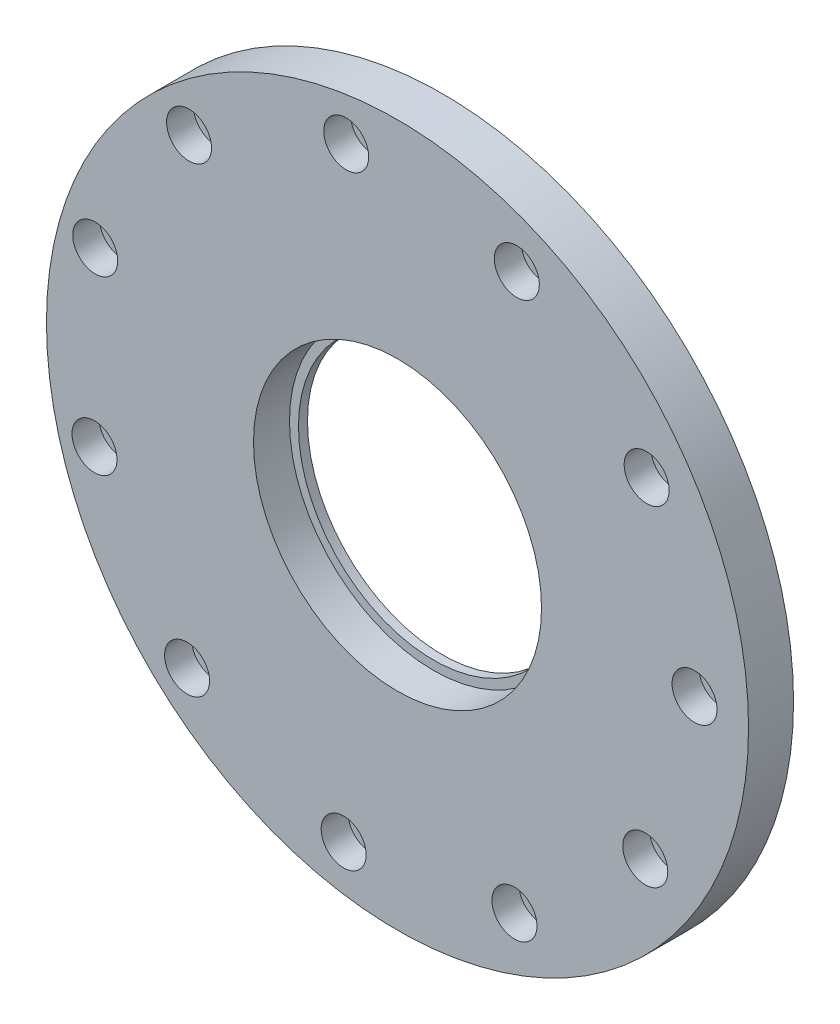
SolidWorks part; units mm, degrees
ref_plane "Front Plane" through (0, 0, 0) normal (0, 0, 1) x (1, 0, 0)
ref_plane "Top Plane" through (0, 0, 0) normal (0, 1, 0) x (1, 0, 0)
ref_plane "Right Plane" through (0, 0, 0) normal (1, 0, 0) x (0, 0, -1)
sketch "Sketch1" plane through (0, 0, 0) normal (0, 0, 1) x (1, 0, 0)
  circle A0 centre (0, 0) radius 39
  circle A1 centre (0, 0) radius 33 construction
  circle A2 centre (33, 0) radius 2.5
  circle A3 centre (27.5249, -18.359) radius 2.5
  circle A4 centre (12.9933, -30.8434) radius 2.5
  circle A5 centre (-5.981, -33.4897) radius 2.5
  circle A6 centre (-23.3739, -25.4576) radius 2.5
  circle A7 centre (-33.6633, -9.2972) radius 2.5
  circle A8 centre (-33.5823, 9.8606) radius 2.5
  circle A9 centre (-23.1566, 25.9334) radius 2.5
  circle A10 centre (-5.6964, 33.8182) radius 2.5
  circle A11 centre (13.2549, 31.0115) radius 2.5
  circle A12 centre (27.6804, 18.4046) radius 2.5
  circle A13 centre (0, 0) radius 16
  point P7 (-1, 0)
  point P28 (-1, 0.1438)
extrude "Boss-Extrude1" add sketch "Sketch1" along normal blind 3
sketch "Sketch2" plane through (0, 0, 0) normal (0, 0, -1) x (-1, 0, 0)
  circle A0 centre (0, 0) radius 16
  circle A1 centre (0, 0) radius 39
  dimension "D1" = 32
extrude "Boss-Extrude2" add sketch "Sketch2" along normal blind 2 contours A1 | A0
sketch "Sketch3" plane through (0, 0, 3) normal (0, 0, 1) x (1, 0, 0)
  circle A0 centre (33, 0) radius 1.6
  circle A1 centre (27.5249, -18.359) radius 1.6
  circle A2 centre (12.9933, -30.8434) radius 1.6
  circle A3 centre (-5.981, -33.4897) radius 1.6
  circle A4 centre (-23.3739, -25.4576) radius 1.6
  circle A5 centre (-33.6633, -9.2972) radius 1.6
  circle A6 centre (-33.5823, 9.8606) radius 1.6
  circle A7 centre (-23.1566, 25.9334) radius 1.6
  circle A8 centre (-5.6964, 33.8182) radius 1.6
  circle A9 centre (13.2549, 31.0115) radius 1.6
  circle A10 centre (27.6804, 18.4046) radius 1.6
  point P25 (-1, 0.1438)
  dimension "D1" = 3.2
  dimension "D2" = 11
extrude "Cut-Extrude1" cut sketch "Sketch3" against normal through all
sketch "Sketch4" plane through (0, 0, -2) normal (0, 0, -1) x (-1, 0, 0)
  circle A0 centre (0, 0) radius 16
  circle A1 centre (0, 0) radius 15
  dimension "D1" = 32
  dimension "D2" = 30
extrude "Boss-Extrude3" add sketch "Sketch4" against normal blind 1
